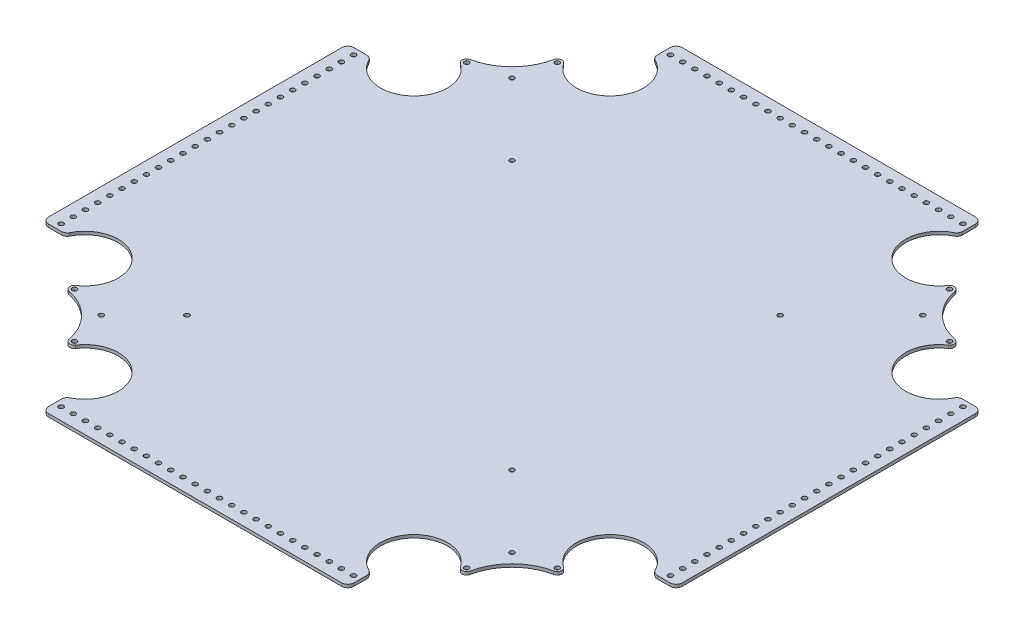
SolidWorks part; units mm, degrees
material "PC High Viscosity"
ref_plane "Front Plane" through (0, 0, 0) normal (0, 0, 1) x (1, 0, 0)
ref_plane "Top Plane" through (0, 0, 0) normal (0, 1, 0) x (1, 0, 0)
ref_plane "Right Plane" through (0, 0, 0) normal (1, 0, 0) x (0, 0, -1)
sketch "Sketch1" plane through (0, 0, 0) normal (0, 1, 0) x (1, 0, 0)
  line L1 (330.2, 330.2) -> (-330.2, 330.2)
  line L2 (330.2, 330.2) -> (330.2, -330.2)
  line L3 (330.2, -330.2) -> (-330.2, -330.2)
  line L4 (-330.2, 330.2) -> (-330.2, -330.2)
  line L5 (330.2, 330.2) -> (-330.2, -330.2) construction
  line L6 (330.2, -330.2) -> (-330.2, 330.2) construction
  point P0 (0, 0)
  dimension "D1" = 660.4
extrude "Boss-Extrude1" add sketch "Sketch1" along normal mid plane 3.175
sketch "Sketch2" plane through (0, 1.5875, 0) normal (0, 1, 0) x (1, 0, 0)
  line L0 (-330.2, -330.2) -> (330.2, -330.2) construction
  line L1 (-330.2, 330.2) -> (-330.2, -330.2) construction
  circle A0 centre (-317.5, -317.5) radius 2.4892
  dimension "D1" = 4.9784
  dimension "D2" = 12.7
  dimension "D3" = 12.7
extrude "Cut-Extrude1" cut sketch "Sketch2" against normal through all
pattern_linear "LPattern1" count 51 spacing 12.7 along (0, 0, -1) count 51 spacing 12.7 along (1, 0, 0) of "Cut-Extrude1" pattern seed only yes
pattern_linear "LPattern2" count 51 spacing 12.7 along (0, 0, -1) of face at (317.5, -1.5875, 319.9892)
pattern_linear "LPattern3" count 50 spacing 12.7 along (1, 0, 0) of face at (-317.5, -1.5875, -315.0108)
sketch "Sketch4" plane through (0, -1.5875, 0) normal (0, -1, 0) x (-1, 0, 0)
  line L0 (-330.2, 159.131) -> (-306.3652, 159.131)
  line L1 (-330.2, -330.2) -> (-330.2, 330.2) construction
  line L2 (-320.675, 160.7185) -> (-314.325, 160.7185) construction
  line L3 (-159.131, 330.2) -> (-159.131, 306.3652)
  line L4 (-330.2, 330.2) -> (330.2, 330.2) construction
  line L5 (-159.131, 330.2) -> (-330.2, 330.2)
  line L6 (-330.2, 330.2) -> (-330.2, 159.131)
  circle A0 centre (-263.525, 263.525) radius 55.5625
  arc A1 (-232.9401, 309.912) -> (-319.0875, 263.525) centre (-263.525, 263.525) ccw construction
  circle A2 centre (-171.45, 273.685) radius 34.925
  circle A3 centre (-273.685, 171.45) radius 34.925
  arc A4 (-140.716, 273.685) -> (-171.45, 304.419) centre (-171.45, 273.685) ccw construction
  arc A5 (-304.8, 171.45) -> (-251.6834, 149.4484) centre (-273.685, 171.45) ccw construction
  arc A6 (-254.2153, 200.4446) -> (-252.5049, 209.0663) centre (-251.5604, 204.3984) cw
  arc A7 (-209.0663, 252.5049) -> (-200.4446, 254.2153) centre (-204.3984, 251.5604) cw
  dimension "D1" = 69.85
  dimension "D2" = 1.5875
  dimension "D3" = 4.7625
extrude "Cut-Extrude2" cut sketch "Sketch4" against normal through all contours A0 A7 A2 L3 L5 L6 L0 A3 A6 | A0 | A3 | A2 region at (327.7807, -1.5875, -244.6655) region at (273.685, -1.5875, -171.45) region at (263.525, -1.5875, -263.525) region at (171.45, -1.5875, -273.685)
mirror "Mirror2" about plane through (0, 0, 0) normal (1, 0, 0) of "Cut-Extrude2"
mirror "Mirror3" about plane through (0, 0, 0) normal (0, 0, 1) of "Cut-Extrude2", "Mirror2"
fillet "Fillet1" radius 6.35 16 edges at (-330.2, 0, -159.131) (-306.3652, 0, -159.131) (-159.131, 0, -306.3652) (-159.131, 0, -330.2) (159.131, 0, -330.2) (159.131, 0, -306.3652) (306.3652, 0, -159.131) (330.2, 0, -159.131) (330.2, 0, 159.131) (306.3652, 0, 159.131) (159.131, 0, 306.3652) (159.131, 0, 330.2) (-159.131, 0, 330.2) (-159.131, 0, 306.3652) (-330.2, 0, 159.131) (-306.3652, 0, 159.131)
sketch "Sketch5" plane through (0, -1.5875, 0) normal (0, -1, 0) x (1, 0, 0)
  circle A4 centre (139.7, 139.7) radius 2.4892
  circle A5 centre (139.7, -139.7) radius 2.4892
  circle A6 centre (-139.7, -139.7) radius 2.4892
  circle A8 centre (-169.3333, 169.3333) radius 2.4892
  circle A9 centre (-169.3333, 169.3333) radius 2.4892 construction
  circle A10 centre (-139.7, -139.7) radius 2.4892 construction
  circle A11 centre (139.7, -139.7) radius 2.4892 construction
  circle A12 centre (139.7, 139.7) radius 2.4892 construction
  dimension "D1" = 4.9784
extrude "Cut-Extrude3" cut sketch "Sketch5" against normal through all
sketch "Sketch6" plane through (0, 1.5875, 0) normal (0, 1, 0) x (1, 0, 0)
  line L0 (0, 0) -> (0, 23.3452) construction
  line L1 (0, 0) -> (30.1444, 0) construction
  circle A0 centre (-251.5604, -204.3984) radius 2.4892
  circle A1 centre (-204.3984, -251.5604) radius 2.4892
  circle A2 centre (-169.3333, -169.3333) radius 2.4892 construction
  circle A4 centre (-214.0672, -214.0672) radius 2.4892
  arc A5 (-251.5604, -204.3984) -> (-204.3984, -251.5604) centre (-241.0079, -241.0079) cw construction
  arc A6 (251.5604, -204.3984) -> (204.3984, -251.5604) centre (241.0079, -241.0079) ccw construction
  circle A7 centre (214.0672, -214.0672) radius 2.4892
  circle A8 centre (204.3984, -251.5604) radius 2.4892
  circle A9 centre (251.5604, -204.3984) radius 2.4892
  arc A10 (251.5604, 204.3984) -> (204.3984, 251.5604) centre (241.0079, 241.0079) cw construction
  arc A11 (-251.5604, 204.3984) -> (-204.3984, 251.5604) centre (-241.0079, 241.0079) ccw construction
  circle A12 centre (251.5604, 204.3984) radius 2.4892
  circle A13 centre (204.3984, 251.5604) radius 2.4892
  circle A14 centre (214.0672, 214.0672) radius 2.4892
  circle A15 centre (-214.0672, 214.0672) radius 2.4892
  circle A16 centre (-204.3984, 251.5604) radius 2.4892
  circle A17 centre (-251.5604, 204.3984) radius 2.4892
  dimension "D1" = 38.1
extrude "Cut-Extrude4" cut sketch "Sketch6" against normal through all both
